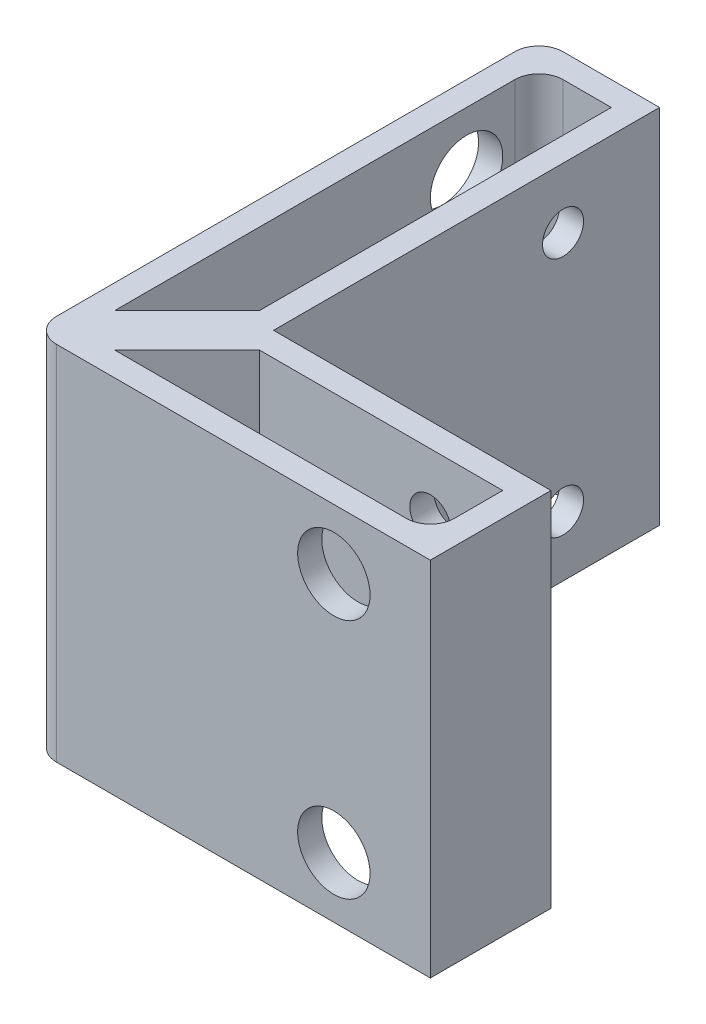
SolidWorks part; units mm, degrees
ref_plane "Front Plane" through (0, 0, 0) normal (0, 0, 1) x (1, 0, 0)
ref_plane "Top Plane" through (0, 0, 0) normal (0, 1, 0) x (1, 0, 0)
ref_plane "Right Plane" through (0, 0, 0) normal (1, 0, 0) x (0, 0, -1)
ref_axis "X" through (-88.99, 0, 0) along (1, 0, 0)
ref_axis "Y" through (0, 55, 0) along (0, -1, 0)
ref_axis "Z" through (0, 0, -88.99) along (0, 0, 1)
sketch "Sketch1" plane through (0, 0, 0) normal (0, 1, 0) x (1, 0, 0)
  line L0 (0, 0) -> (0, 24)
  line L1 (0, 0) -> (15, 0)
  line L2 (15, 0) -> (23, 0)
  line L3 (23, 0) -> (23, -10)
  line L4 (23, -10) -> (-10, -10)
  line L5 (-10, -10) -> (-10, 32)
  line L6 (-10, 32) -> (0, 32)
  line L7 (0, 32) -> (0, 24)
  line L8 (-2, 30) -> (-2, 24)
  line L9 (-2, -2) -> (-2, 24)
  line L10 (-2, -2) -> (15, -2)
  line L11 (15, -2) -> (21, -2)
  line L12 (21, -2) -> (21, -8)
  line L13 (21, -8) -> (-8, -8)
  line L14 (-8, -8) -> (-8, 30)
  line L15 (-8, 30) -> (-2, 30)
  line L16 (-2, -2) -> (-8, -8) construction
  line L17 (-5.1716, -8) -> (0.8284, -2)
  line L18 (-2, 0.8284) -> (-8, -5.1716)
  point P21 (-5, -2.7942)
  point P22 (0, 0)
  dimension "D1" = 24
  dimension "D2" = 15
  dimension "D3" = 8
  dimension "D4" = 2
  dimension "D5" = 10
  dimension "D6" = 2
  dimension "D7" = 2
extrude "Boss-Extrude1" add sketch "Sketch1" along normal mid plane 30 contours L7 L6 L5 L4 L3 L2 L1 L0 L14 L15 L9 L10 L12 L13 | L16 L9 L18 L14 | L10 L16 L13 L17 region at (7.5, 0, 0.5341) region at (-5, 0, 3.5858) region at (-3.5858, 0, 5)
fillet "Fillet1" radius 2 4 edges at (-10, 0, -32) (-10, 0, 10) (21, 0, 8) (-8, 0, -30)
hole_wizard "M3 Clearance Hole1" positions "3DSketch1" profile "Sketch2" hole size "M3" standard "ANSI Metric" end condition through all
sketch3d "3DSketch1"
  line L0 (0, 0, -24) -> (0, 10, -24) construction
  line L3 (0, 0, -24) -> (0, -10, -24) construction
  line L6 (15, 0, 0) -> (15, 10, 0) construction
  line L7 (15, 0, 0) -> (23, 0, 0) construction
  line L10 (15, 0, 0) -> (15, -10, 0) construction
  point P37 (0, 10, -24)
  point P39 (0, -10, -24)
  point P41 (15, 10, 0)
  point P43 (15, -10, 0)
  point P46 (0, 0, 0)
  point P47 (0, 0, 0)
  point P48 (15, 10, 0)
  point P49 (15, -10, 0)
  point P50 (0, 10, -24)
  point P51 (0, -10, -24)
  dimension "D1" = 10
sketch "Sketch2" plane through (15, -10, 0) normal (1, 0, 0) x (0, 1, 0)
  line L0 (0, 0) -> (0, 10)
  line L1 (0, 10) -> (1.7, 10)
  line L2 (1.7, 10) -> (1.7, 0)
  line L5 (1.7, 0) -> (0, 0)
  line L11 (0, -6.35) -> (0, 107.95) construction
  dimension "Thru Hole Dia." = 3.4
  dimension "Thru Hole Depth" = 10
sketch "Sketch3" plane through (-10, 0, 0) normal (-1, 0, 0) x (0, 0, 1)
  circle A0 centre (-24, -10) radius 1.7 construction
  circle A1 centre (-24, 10) radius 1.7 construction
  circle A2 centre (-24, -10) radius 1.7 construction
  circle A3 centre (-24, 10) radius 1.7 construction
  circle A4 centre (-24, 10) radius 3
  circle A5 centre (-24, -10) radius 3
  dimension "D1" = 6
extrude "Cut-Extrude1" cut sketch "Sketch3" against normal up to surface (8 mm away) up to face at (-2, 10, -25.7)
sketch "Sketch4" plane through (0, 0, 10) normal (0, 0, 1) x (1, 0, 0)
  circle A0 centre (15, -10) radius 1.7 construction
  circle A1 centre (15, 10) radius 1.7 construction
  circle A2 centre (15, -10) radius 1.7 construction
  circle A3 centre (15, 10) radius 1.7 construction
  circle A4 centre (15, 10) radius 3
  circle A5 centre (15, -10) radius 3
  dimension "D1" = 6
extrude "Cut-Extrude2" cut sketch "Sketch4" against normal up to surface (8 mm away) up to face at (13.3, 10, 2)
